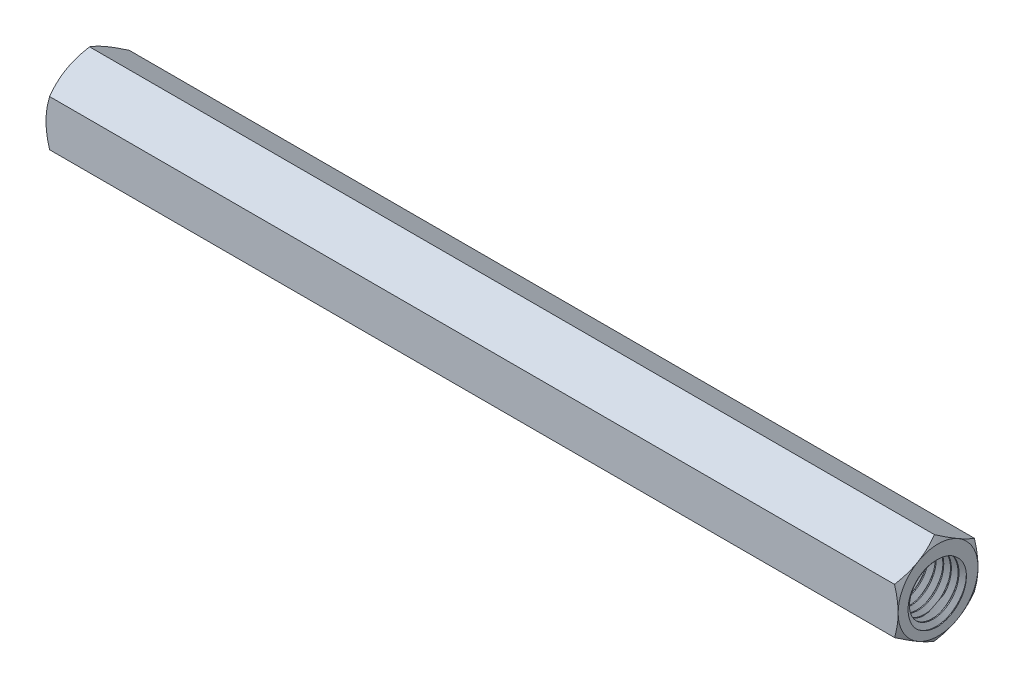
SolidWorks part; units mm, degrees
note: '?' marks a value the reader was unsure of.
ref_plane "Front Plane" through (0, 0, 0) normal (0, 0, 1) x (1, 0, 0)
ref_plane "Top Plane" through (0, 0, 0) normal (0, 1, 0) x (1, 0, 0)
ref_plane "Right Plane" through (0, 0, 0) normal (1, 0, 0) x (0, 0, -1)
sketch "Sketch1" plane through (0, 0, 0) normal (0, 0, 1) x (1, 0, 0)
  line L0 (-50.8, 0) -> (50.8, 0) construction
  line L1 (-50.8, 3.175) -> (-50.8, -3.175) construction
  line L2 (50.8, 3.175) -> (50.8, -3.175) construction
  line L3 (0, 4.7625) -> (0, -4.7625) construction
  line L4 (31.75, 3.175) -> (31.75, -3.175) construction
  line L5 (-31.75, 3.175) -> (-31.75, -3.175) construction
  line L6 (-50.8, 3.175) -> (-31.75, 3.175) construction
  line L7 (-50.8, -3.175) -> (-31.75, -3.175) construction
  line L8 (31.75, -3.175) -> (50.8, -3.175) construction
  line L9 (31.75, 3.175) -> (50.8, 3.175) construction
  point P7 (-31.75, 0)
  point P8 (31.75, 0)
  point P17 (43.5429, -3.175)
  dimension "Length" = 101.6
  dimension "D1" = 19.05
  dimension "Thread Size" = 6.35
  dimension "Rod OD" = 9.525
  dimension "Thread Length" = 19.05
  dimension "D2" = 63.5
  dimension "D5" = 7.2571
sketch "Sketch2" plane through (0, 0, 0) normal (1, 0, 0) x (0, 0, -1)
  line L1 (4.7625, 2.7496) -> (0, 5.4993)
  line L2 (0, 5.4993) -> (-4.7625, 2.7496)
  line L3 (-4.7625, 2.7496) -> (-4.7625, -2.7496)
  line L4 (-4.7625, -2.7496) -> (0, -5.4993)
  line L5 (0, -5.4993) -> (4.7625, -2.7496)
  line L6 (4.7625, -2.7496) -> (4.7625, 2.7496)
  circle A1 centre (0, 0) radius 4.7625 construction
  point P12 (0, 4.7625)
extrude "Boss-Extrude1" add sketch "Sketch2" against normal up to vertex (50.8 mm away) and the other way up to vertex (50.8 mm away) up to point (-50.8, 0, 0) other way up to point (50.8, 0, 0)
sketch "Sketch4" plane through (-50.8, 0, 0) normal (-1, 0, 0) x (0, 0, 1)
  circle A0 centre (0, 0) radius 3.175
extrude "Cut-Extrude1" cut sketch "Sketch4" against normal up to vertex (19.05 mm away) up to point (-31.75, 0, 0)
sketch "Sketch7" plane through (-31.75, 0, 0) normal (-1, 0, 0) x (0, 0, 1)
  circle A1 centre (0, 0) radius 3.175
  circle A2 centre (0, 0) radius 3.175
  dimension "D1" = 0
extrude "Cut-Extrude2" cut sketch "Sketch7" against normal through all draft 59
sketch "Sketch5" plane through (-50.8, 0, 0) normal (-1, 0, 0) x (0, 0, 1)
  line L0 (0, 5.4993) -> (4.7625, 2.7496) construction
  circle A0 centre (0, 0) radius 4.7625
extrude "Cut-Extrude-Thin2" cut sketch "Sketch5" against normal through all draft 60 thin
mirror "Mirror1" about plane through (0, 0, 0) normal (1, 0, 0) of "Cut-Extrude1", "Cut-Extrude-Thin2", "Cut-Extrude2"
sketch "Sketch3" plane through (-50.8, 0, 0) normal (1, 0, 0) x (0, 0, -1)
  circle A0 centre (0, 0) radius 3.175 construction
  circle A1 centre (0, 0) radius 3.175
curve "Helix/Spiral1" pitch 0.9071 height 19.05 turns 21 parameters "pitch"=0.9071
sketch "Sketch6" plane through (0, 0, 0) normal (0, 0, 1) x (1, 0, 0)
  line L0 (-51.6504, 3.0768) -> (-50.7433, 3.0768) construction
  line L1 (-50.7433, 3.0768) -> (-51.1969, 3.8624) construction
  line L2 (-51.1969, 3.8624) -> (-51.6504, 3.0768) construction
  line L3 (-51.5937, 3.175) -> (-50.8, 3.175) construction
  line L4 (-51.1969, 3.0768) -> (-51.1969, 3.175) construction
  line L5 (-51.6221, 3.1259) -> (-50.7717, 3.1259) construction
  line L6 (-51.2536, 3.7642) -> (-51.1402, 3.7642) construction
  line L7 (-51.1969, 3.7642) -> (-51.1969, 3.8624) construction
  line L8 (-51.2536, 3.7642) -> (-51.1402, 3.7642) construction
  line L10 (-51.2536, 3.7642) -> (-51.6221, 3.1259)
  line L11 (-51.6221, 3.1259) -> (-50.7717, 3.1259)
  line L12 (-50.7717, 3.1259) -> (-51.1402, 3.7642)
  line L13 (-51.2536, 3.7642) -> (-51.1402, 3.7642)
  point P10 (-51.1969, 3.1259)
  dimension "D1" = 0.9071
  dimension "D2" = 0.1134
sweep "Cut-Sweep1" cut profiles "Sketch6" path "Helix/Spiral1"
mirror "Mirror2" about plane through (0, 0, 0) normal (1, 0, 0) of "Cut-Sweep1"
ref_axis "Center Axis 1" through (-84.6505, 0, 0) along (1, 0, 0)?
ref_plane "Contact Plane 1" through (-50.8, 0, 0) normal (-1, 0, 0) x (0, 0, 1)
ref_plane "Contact Plane 2" through (50.8, 0, 0) normal (1, 0, 0) x (0, 0, -1)
equation "\"D1@Sketch1\" = \"Thread Length@Sketch1\""
equation "\"D3@Helix/Spiral1\"=\"Thread Length@Sketch1\""
equation "\"D5@Sketch1\" = \"pitch@Helix/Spiral1\"*8"
equation "\"D1@Sketch6\"=\"pitch@Helix/Spiral1\""
equation "\"D2@Sketch6\"=\"D1@Sketch6\"/ 1/8"
